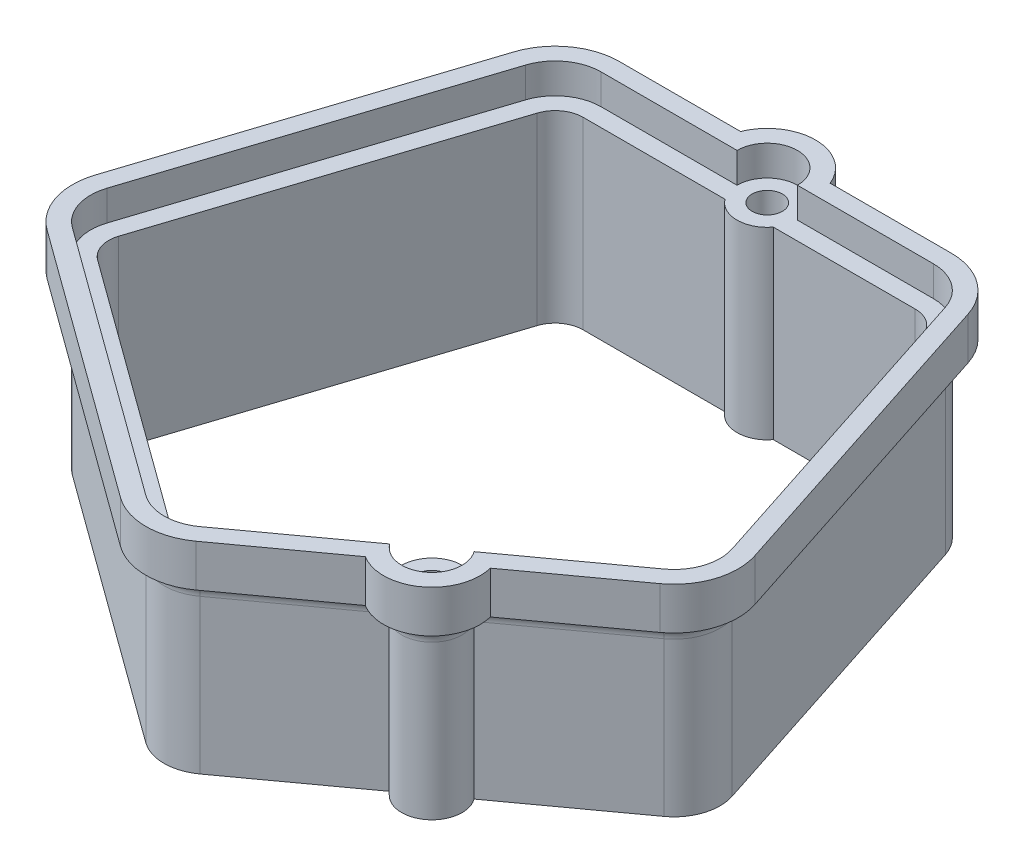
SolidWorks part; units mm, degrees
material "ABS"
ref_plane "Front Plane" through (0, 0, 0) normal (0, 0, 1) x (1, 0, 0)
ref_plane "Top Plane" through (0, 0, 0) normal (0, 1, 0) x (1, 0, 0)
ref_plane "Right Plane" through (0, 0, 0) normal (1, 0, 0) x (0, 0, -1)
sketch "Sketch1" plane through (0, 0, 0) normal (0, 1, 0) x (1, 0, 0)
  line L0 (-42.9604, -16.814) -> (1.5332, -49.1405)
  line L1 (6.9643, -49.1405) -> (25.975, -35.3284)
  line L2 (4.2488, 51.849) -> (4.2488, 50.849)
  line L3 (0.2488, 46.849) -> (-23.2498, 46.849)
  line L4 (-30.4968, 41.5837) -> (-47.4919, -10.7216)
  line L5 (-44.7237, -19.241) -> (-0.2302, -51.5675)
  line L6 (8.7277, -51.5675) -> (27.7384, -37.7554)
  line L7 (33.3256, -38.6403) -> (33.9134, -39.4494)
  line L8 (35.0196, -32.4654) -> (53.2213, -19.241)
  line L9 (55.9894, -10.7216) -> (38.9943, 41.5837)
  line L10 (31.7473, 46.849) -> (9.2488, 46.849)
  line L11 (32.4472, -30.6261) -> (51.4579, -16.814)
  line L12 (53.1362, -11.6487) -> (36.1412, 40.6567)
  line L13 (31.7473, 43.849) -> (8.2488, 43.849)
  line L14 (-23.2498, 43.849) -> (0.2488, 43.849)
  line L15 (-44.6387, -11.6487) -> (-27.6437, 40.6567)
  line L16 (-47.4919, -15.431) -> (47.4919, 15.431) construction
  line L17 (-44.6387, -14.504) -> (44.6387, 14.504) construction
  arc A0 (9.2488, 46.849) -> (4.2488, 51.849) centre (4.2488, 46.849) ccw
  arc A1 (4.2488, 50.849) -> (0.2488, 46.849) centre (4.2488, 46.849) ccw
  arc A2 (-23.2498, 46.849) -> (-30.4968, 41.5837) centre (-23.2498, 39.229) ccw
  arc A3 (-47.4919, -10.7216) -> (-44.7237, -19.241) centre (-40.2448, -13.0763) ccw
  arc A4 (-0.2302, -51.5675) -> (8.7277, -51.5675) centre (4.2488, -45.4028) ccw
  arc A5 (27.7384, -37.7554) -> (33.3256, -38.6403) centre (30.9745, -35.4043) ccw
  arc A6 (33.9134, -39.4494) -> (35.0196, -32.4654) centre (30.9745, -35.4043) ccw
  arc A7 (53.2213, -19.241) -> (55.9894, -10.7216) centre (48.7423, -13.0763) ccw
  arc A8 (38.9943, 41.5837) -> (31.7473, 46.849) centre (31.7473, 39.229) ccw
  arc A9 (-44.6387, -11.6487) -> (-42.9604, -16.814) centre (-40.2448, -13.0763) ccw
  arc A10 (1.5332, -49.1405) -> (6.9643, -49.1405) centre (4.2488, -45.4028) ccw
  circle A11 centre (30.9745, -35.4043) radius 2.5
  arc A12 (32.4472, -30.6261) -> (25.975, -35.3284) centre (30.9745, -35.4043) ccw
  arc A13 (51.4579, -16.814) -> (53.1362, -11.6487) centre (48.7423, -13.0763) ccw
  arc A14 (36.1412, 40.6567) -> (31.7473, 43.849) centre (31.7473, 39.229) ccw
  arc A15 (0.2488, 43.849) -> (8.2488, 43.849) centre (4.2488, 46.849) ccw
  circle A16 centre (4.2488, 46.849) radius 2.5
  arc A17 (-23.2498, 43.849) -> (-27.6437, 40.6567) centre (-23.2498, 39.229) ccw
  arc A36 (4.2488, 51.849) -> (-0.7512, 46.849) centre (4.2488, 46.849) ccw
  arc A37 (33.9134, -39.4494) -> (26.9294, -38.3432) centre (30.9745, -35.4043) cw
  point P58 (0, 0)
  point P60 (0, 0)
extrude "Boss-Extrude1" add sketch "Sketch1" along normal blind 40 contours L9 A8 L10 A0 L2 A1 L3 A2 L4 A3 L5 A4 L6 A5 L7 A6 L8 A7 A17 L14 A15 L13 A14 L12 A13 L11 A12 L1 A10 L0 A9 L15 A16 A11 | A37 L7 A5 L6 | L2 A36 L3 A1 region at (6.7388, 0, -49.339) region at (1.3722, 0, -49.7256) region at (30.3381, 0, 39.4223)
sketch "Sketch2" plane through (0, 40, 0) normal (0, 1, 0) x (1, 0, 0)
  line L1 (-30.4968, 41.5837) -> (-33.35, 42.5108)
  line L2 (-47.4919, -10.7216) -> (-50.345, -9.7946)
  line L3 (-33.35, 42.5108) -> (-50.345, -9.7946)
  line L5 (-23.2498, 46.849) -> (-23.2498, 49.849)
  line L8 (55.9894, -10.7216) -> (38.9943, 41.5837)
  line L9 (31.7473, 46.849) -> (9.2488, 46.849)
  line L10 (-0.7512, 46.849) -> (-23.2498, 46.849)
  line L13 (-30.4968, 41.5837) -> (-47.4919, -10.7216)
  line L21 (-44.7237, -19.241) -> (-0.2302, -51.5675)
  line L22 (8.7277, -51.5675) -> (26.9294, -38.3432)
  line L23 (35.0196, -32.4654) -> (53.2213, -19.241)
  line L24 (55.9894, -10.7216) -> (38.9943, 41.5837)
  line L25 (31.7473, 46.849) -> (9.2488, 46.849)
  line L26 (-0.7512, 46.849) -> (-23.2498, 46.849)
  line L27 (-30.4968, 41.5837) -> (-47.4919, -10.7216)
  line L28 (-44.7237, -19.241) -> (-0.2302, -51.5675)
  line L29 (8.7277, -51.5675) -> (26.9294, -38.3432)
  line L30 (35.0196, -32.4654) -> (53.2213, -19.241)
  line L31 (-23.2498, 49.849) -> (-3.1674, 49.849)
  line L33 (54.9846, -21.6681) -> (38.7377, -33.4722)
  line L34 (10.491, -53.9946) -> (26.738, -42.1905)
  line L35 (-1.9935, -53.9946) -> (-46.4871, -21.6681)
  line L36 (31.7473, 49.849) -> (11.665, 49.849)
  line L37 (41.8475, 42.5108) -> (58.8425, -9.7946)
  arc A0 (-3.1674, 49.849) -> (11.665, 49.849) centre (4.2488, 46.849) cw
  arc A1 (-33.35, 42.5108) -> (-23.2498, 49.849) centre (-23.2498, 39.229) cw
  arc A3 (-50.345, -9.7946) -> (-46.4871, -21.6681) centre (-40.2448, -13.0763) ccw
  arc A5 (41.8475, 42.5108) -> (31.7473, 49.849) centre (31.7473, 39.229) ccw
  arc A6 (58.8425, -9.7946) -> (54.9846, -21.6681) centre (48.7423, -13.0763) cw
  arc A21 (26.738, -42.1905) -> (38.7377, -33.4722) centre (30.9745, -35.4043) ccw
  arc A22 (-1.9935, -53.9946) -> (10.491, -53.9946) centre (4.2488, -45.4028) ccw
  arc A23 (38.9943, 41.5837) -> (31.7473, 46.849) centre (31.7473, 39.229) ccw
  arc A24 (9.2488, 46.849) -> (-0.7512, 46.849) centre (4.2488, 46.849) ccw
  arc A25 (-23.2498, 46.849) -> (-30.4968, 41.5837) centre (-23.2498, 39.229) ccw
  arc A26 (-47.4919, -10.7216) -> (-44.7237, -19.241) centre (-40.2448, -13.0763) ccw
  arc A27 (-0.2302, -51.5675) -> (8.7277, -51.5675) centre (4.2488, -45.4028) ccw
  arc A28 (26.9294, -38.3432) -> (35.0196, -32.4654) centre (30.9745, -35.4043) ccw
  arc A29 (53.2213, -19.241) -> (55.9894, -10.7216) centre (48.7423, -13.0763) ccw
  arc A30 (38.9943, 41.5837) -> (31.7473, 46.849) centre (31.7473, 39.229) ccw
  arc A31 (9.2488, 46.849) -> (-0.7512, 46.849) centre (4.2488, 46.849) ccw
  arc A32 (-23.2498, 46.849) -> (-30.4968, 41.5837) centre (-23.2498, 39.229) ccw
  arc A33 (-47.4919, -10.7216) -> (-44.7237, -19.241) centre (-40.2448, -13.0763) ccw
  arc A34 (-0.2302, -51.5675) -> (8.7277, -51.5675) centre (4.2488, -45.4028) ccw
  arc A35 (26.9294, -38.3432) -> (35.0196, -32.4654) centre (30.9745, -35.4043) ccw
  arc A36 (53.2213, -19.241) -> (55.9894, -10.7216) centre (48.7423, -13.0763) ccw
  line M62 (55.9894, -10.7216) -> (38.9943, 41.5837)
  arc M63 (38.9943, 41.5837) -> (31.7473, 46.849) centre (31.7473, 39.229) ccw
  line M64 (31.7473, 46.849) -> (9.2488, 46.849)
  arc M65 (9.2488, 46.849) -> (-0.7512, 46.849) centre (4.2488, 46.849) ccw
  line M66 (-0.7512, 46.849) -> (-23.2498, 46.849)
  arc M67 (-23.2498, 46.849) -> (-30.4968, 41.5837) centre (-23.2498, 39.229) ccw
  line M68 (-30.4968, 41.5837) -> (-47.4919, -10.7216)
  arc M69 (-47.4919, -10.7216) -> (-44.7237, -19.241) centre (-40.2448, -13.0763) ccw
  line M70 (-44.7237, -19.241) -> (-0.2302, -51.5675)
  arc M71 (-0.2302, -51.5675) -> (8.7277, -51.5675) centre (4.2488, -45.4028) ccw
  line M72 (8.7277, -51.5675) -> (26.9294, -38.3432)
  arc M73 (26.9294, -38.3432) -> (35.0196, -32.4654) centre (30.9745, -35.4043) ccw
  line M74 (35.0196, -32.4654) -> (53.2213, -19.241)
  arc M75 (53.2213, -19.241) -> (55.9894, -10.7216) centre (48.7423, -13.0763) ccw
  dimension "D5" = 3
  dimension "D2" = 3
  dimension "D3" = 3
  dimension "D1" = 0
extrude "Boss-Extrude2" add sketch "Sketch2" along normal blind 5 and the other way blind 2 contours L1 L3 L2 M68 | L35 A22 L34 A21 L33 A6 L37 A5 L36 A0 L31 L5 L2 A3 M66 M65 M64 M63 M62 M75 M74 M73 M72 M71 M70 M69 | A1 L1 L5 M67 region at (-40.4209, 40, -15.8946) region at (-28.3098, 40, -46.1935) region at (-48.9788, 40, 15.9142)
fillet "Fillet1" radius 3 14 edges at (20.498, 38, -46.849) (36.2262, 38, -45.3937) (47.4919, 38, -15.431) (55.9894, 38, 15.431) (-12.0005, 38, -46.849) (-27.7287, 38, -45.3937) (-38.9943, 38, -15.431) (-47.4919, 38, 15.431) (17.8285, 38, 44.9554) (4.2488, 38, 53.0228) (4.2488, 38, -51.849) (33.9134, 38, 39.4494) (44.1204, 38, 25.8532) (-22.477, 38, 35.4043)
sketch "Sketch3" plane through (0, 0, 0) normal (0, -1, 0) x (1, 0, 0)
  line L7 (-44.6387, 11.6487) -> (-27.6437, -40.6567)
  line L8 (1.5332, 49.1405) -> (-42.9604, 16.814)
  line L9 (25.975, 35.3284) -> (6.9643, 49.1405)
  line L10 (51.4579, 16.814) -> (32.4472, 30.6261)
  line L11 (36.1412, -40.6567) -> (53.1362, 11.6487)
  line L12 (8.2488, -43.849) -> (31.7473, -43.849)
  line L13 (-23.2498, -43.849) -> (0.2488, -43.849)
  line L14 (-44.6387, 11.6487) -> (-27.6437, -40.6567)
  line L15 (1.5332, 49.1405) -> (-42.9604, 16.814)
  line L16 (25.975, 35.3284) -> (6.9643, 49.1405)
  line L17 (51.4579, 16.814) -> (32.4472, 30.6261)
  line L18 (36.1412, -40.6567) -> (53.1362, 11.6487)
  line L19 (8.2488, -43.849) -> (31.7473, -43.849)
  line L20 (-23.2498, -43.849) -> (0.2488, -43.849)
  line L21 (38.9943, -41.5837) -> (55.9894, 10.7216)
  line L22 (53.2213, 19.241) -> (35.0196, 32.4654)
  line L23 (26.9294, 38.3432) -> (8.7277, 51.5675)
  line L24 (-0.2302, 51.5675) -> (-44.7237, 19.241)
  line L25 (-47.4919, 10.7216) -> (-30.4968, -41.5837)
  line L26 (-23.2498, -46.849) -> (-0.7512, -46.849)
  line L27 (9.2488, -46.849) -> (31.7473, -46.849)
  line L28 (38.9943, -41.5837) -> (55.9894, 10.7216)
  line L29 (53.2213, 19.241) -> (35.0196, 32.4654)
  line L30 (26.9294, 38.3432) -> (8.7277, 51.5675)
  line L31 (-0.2302, 51.5675) -> (-44.7237, 19.241)
  line L32 (-47.4919, 10.7216) -> (-30.4968, -41.5837)
  line L33 (-23.2498, -46.849) -> (-0.7512, -46.849)
  line L34 (9.2488, -46.849) -> (31.7473, -46.849)
  circle A1 centre (30.9745, 35.4043) radius 2.5
  circle A2 centre (30.9745, 35.4043) radius 2.5
  circle A3 centre (4.2488, -46.849) radius 2.5
  circle A4 centre (4.2488, -46.849) radius 2.5
  arc A7 (-27.6437, -40.6567) -> (-23.2498, -43.849) centre (-23.2498, -39.229) ccw
  arc A8 (-42.9604, 16.814) -> (-44.6387, 11.6487) centre (-40.2448, 13.0763) ccw
  arc A9 (6.9643, 49.1405) -> (1.5332, 49.1405) centre (4.2488, 45.4028) ccw
  arc A10 (25.975, 35.3284) -> (32.4472, 30.6261) centre (30.9745, 35.4043) ccw
  arc A11 (53.1362, 11.6487) -> (51.4579, 16.814) centre (48.7423, 13.0763) ccw
  arc A12 (31.7473, -43.849) -> (36.1412, -40.6567) centre (31.7473, -39.229) ccw
  arc A13 (8.2488, -43.849) -> (0.2488, -43.849) centre (4.2488, -46.849) ccw
  arc A14 (-27.6437, -40.6567) -> (-23.2498, -43.849) centre (-23.2498, -39.229) ccw
  arc A15 (-42.9604, 16.814) -> (-44.6387, 11.6487) centre (-40.2448, 13.0763) ccw
  arc A16 (6.9643, 49.1405) -> (1.5332, 49.1405) centre (4.2488, 45.4028) ccw
  arc A17 (25.975, 35.3284) -> (32.4472, 30.6261) centre (30.9745, 35.4043) ccw
  arc A18 (53.1362, 11.6487) -> (51.4579, 16.814) centre (48.7423, 13.0763) ccw
  arc A19 (31.7473, -43.849) -> (36.1412, -40.6567) centre (31.7473, -39.229) ccw
  arc A20 (8.2488, -43.849) -> (0.2488, -43.849) centre (4.2488, -46.849) ccw
  arc A25 (55.9894, 10.7216) -> (53.2213, 19.241) centre (48.7423, 13.0763) ccw
  arc A26 (35.0196, 32.4654) -> (26.9294, 38.3432) centre (30.9745, 35.4043) ccw
  arc A27 (8.7277, 51.5675) -> (-0.2302, 51.5675) centre (4.2488, 45.4028) ccw
  arc A28 (-44.7237, 19.241) -> (-47.4919, 10.7216) centre (-40.2448, 13.0763) ccw
  arc A29 (-30.4968, -41.5837) -> (-23.2498, -46.849) centre (-23.2498, -39.229) ccw
  arc A30 (-0.7512, -46.849) -> (9.2488, -46.849) centre (4.2488, -46.849) ccw
  arc A31 (31.7473, -46.849) -> (38.9943, -41.5837) centre (31.7473, -39.229) ccw
  arc A32 (55.9894, 10.7216) -> (53.2213, 19.241) centre (48.7423, 13.0763) ccw
  arc A33 (35.0196, 32.4654) -> (26.9294, 38.3432) centre (30.9745, 35.4043) ccw
  arc A34 (8.7277, 51.5675) -> (-0.2302, 51.5675) centre (4.2488, 45.4028) ccw
  arc A35 (-44.7237, 19.241) -> (-47.4919, 10.7216) centre (-40.2448, 13.0763) ccw
  arc A36 (-30.4968, -41.5837) -> (-23.2498, -46.849) centre (-23.2498, -39.229) ccw
  arc A37 (-0.7512, -46.849) -> (9.2488, -46.849) centre (4.2488, -46.849) ccw
  arc A38 (31.7473, -46.849) -> (38.9943, -41.5837) centre (31.7473, -39.229) ccw
  dimension "D1" = 0
  dimension "D2" = 0
  dimension "D3" = 0
  dimension "D4" = 0
extrude "Boss-Extrude3" add sketch "Sketch3" along normal blind 7
sketch "Sketch4" plane through (0, -7, 0) normal (0, -1, 0) x (1, 0, 0)
  line L7 (-23.2498, -43.849) -> (0.2488, -43.849)
  line L8 (-44.6387, 11.6487) -> (-27.6437, -40.6567)
  line L9 (1.5332, 49.1405) -> (-42.9604, 16.814)
  line L10 (25.975, 35.3284) -> (6.9643, 49.1405)
  line L11 (51.4579, 16.814) -> (32.4472, 30.6261)
  line L12 (36.1412, -40.6567) -> (53.1362, 11.6487)
  line L13 (8.2488, -43.849) -> (31.7473, -43.849)
  line L14 (-23.2498, -43.849) -> (0.2488, -43.849)
  line L15 (-44.6387, 11.6487) -> (-27.6437, -40.6567)
  line L16 (1.5332, 49.1405) -> (-42.9604, 16.814)
  line L17 (25.975, 35.3284) -> (6.9643, 49.1405)
  line L18 (51.4579, 16.814) -> (32.4472, 30.6261)
  line L19 (36.1412, -40.6567) -> (53.1362, 11.6487)
  line L20 (8.2488, -43.849) -> (31.7473, -43.849)
  line L21 (38.9943, -41.5837) -> (55.9894, 10.7216)
  line L22 (53.2213, 19.241) -> (35.0196, 32.4654)
  line L23 (26.9294, 38.3432) -> (8.7277, 51.5675)
  line L24 (-0.2302, 51.5675) -> (-44.7237, 19.241)
  line L25 (-47.4919, 10.7216) -> (-30.4968, -41.5837)
  line L26 (-23.2498, -46.849) -> (-0.7512, -46.849)
  line L27 (9.2488, -46.849) -> (31.7473, -46.849)
  line L28 (38.9943, -41.5837) -> (55.9894, 10.7216)
  line L29 (53.2213, 19.241) -> (35.0196, 32.4654)
  line L30 (26.9294, 38.3432) -> (8.7277, 51.5675)
  line L31 (-0.2302, 51.5675) -> (-44.7237, 19.241)
  line L32 (-47.4919, 10.7216) -> (-30.4968, -41.5837)
  line L33 (-23.2498, -46.849) -> (-0.7512, -46.849)
  line L34 (9.2488, -46.849) -> (31.7473, -46.849)
  circle A1 centre (30.9745, 35.4043) radius 2.5
  circle A2 centre (30.9745, 35.4043) radius 2.5
  circle A3 centre (4.2488, -46.849) radius 2.5
  circle A4 centre (4.2488, -46.849) radius 2.5
  arc A7 (-27.6437, -40.6567) -> (-23.2498, -43.849) centre (-23.2498, -39.229) ccw
  arc A8 (-42.9604, 16.814) -> (-44.6387, 11.6487) centre (-40.2448, 13.0763) ccw
  arc A9 (6.9643, 49.1405) -> (1.5332, 49.1405) centre (4.2488, 45.4028) ccw
  arc A10 (25.975, 35.3284) -> (32.4472, 30.6261) centre (30.9745, 35.4043) ccw
  arc A11 (53.1362, 11.6487) -> (51.4579, 16.814) centre (48.7423, 13.0763) ccw
  arc A12 (31.7473, -43.849) -> (36.1412, -40.6567) centre (31.7473, -39.229) ccw
  arc A13 (8.2488, -43.849) -> (0.2488, -43.849) centre (4.2488, -46.849) ccw
  arc A14 (-27.6437, -40.6567) -> (-23.2498, -43.849) centre (-23.2498, -39.229) ccw
  arc A15 (-42.9604, 16.814) -> (-44.6387, 11.6487) centre (-40.2448, 13.0763) ccw
  arc A16 (6.9643, 49.1405) -> (1.5332, 49.1405) centre (4.2488, 45.4028) ccw
  arc A17 (25.975, 35.3284) -> (32.4472, 30.6261) centre (30.9745, 35.4043) ccw
  arc A18 (53.1362, 11.6487) -> (51.4579, 16.814) centre (48.7423, 13.0763) ccw
  arc A19 (31.7473, -43.849) -> (36.1412, -40.6567) centre (31.7473, -39.229) ccw
  arc A20 (8.2488, -43.849) -> (0.2488, -43.849) centre (4.2488, -46.849) ccw
  arc A25 (31.7473, -46.849) -> (38.9943, -41.5837) centre (31.7473, -39.229) ccw
  arc A26 (55.9894, 10.7216) -> (53.2213, 19.241) centre (48.7423, 13.0763) ccw
  arc A27 (35.0196, 32.4654) -> (26.9294, 38.3432) centre (30.9745, 35.4043) ccw
  arc A28 (8.7277, 51.5675) -> (-0.2302, 51.5675) centre (4.2488, 45.4028) ccw
  arc A29 (-44.7237, 19.241) -> (-47.4919, 10.7216) centre (-40.2448, 13.0763) ccw
  arc A30 (-30.4968, -41.5837) -> (-23.2498, -46.849) centre (-23.2498, -39.229) ccw
  arc A31 (-0.7512, -46.849) -> (9.2488, -46.849) centre (4.2488, -46.849) ccw
  arc A32 (31.7473, -46.849) -> (38.9943, -41.5837) centre (31.7473, -39.229) ccw
  arc A33 (55.9894, 10.7216) -> (53.2213, 19.241) centre (48.7423, 13.0763) ccw
  arc A34 (35.0196, 32.4654) -> (26.9294, 38.3432) centre (30.9745, 35.4043) ccw
  arc A35 (8.7277, 51.5675) -> (-0.2302, 51.5675) centre (4.2488, 45.4028) ccw
  arc A36 (-44.7237, 19.241) -> (-47.4919, 10.7216) centre (-40.2448, 13.0763) ccw
  arc A37 (-30.4968, -41.5837) -> (-23.2498, -46.849) centre (-23.2498, -39.229) ccw
  arc A38 (-0.7512, -46.849) -> (9.2488, -46.849) centre (4.2488, -46.849) ccw
  dimension "D1" = 0
  dimension "D2" = 0
  dimension "D3" = 0
  dimension "D4" = 0
extrude "Cut-Extrude1" cut sketch "Sketch4" against normal blind 16.52
